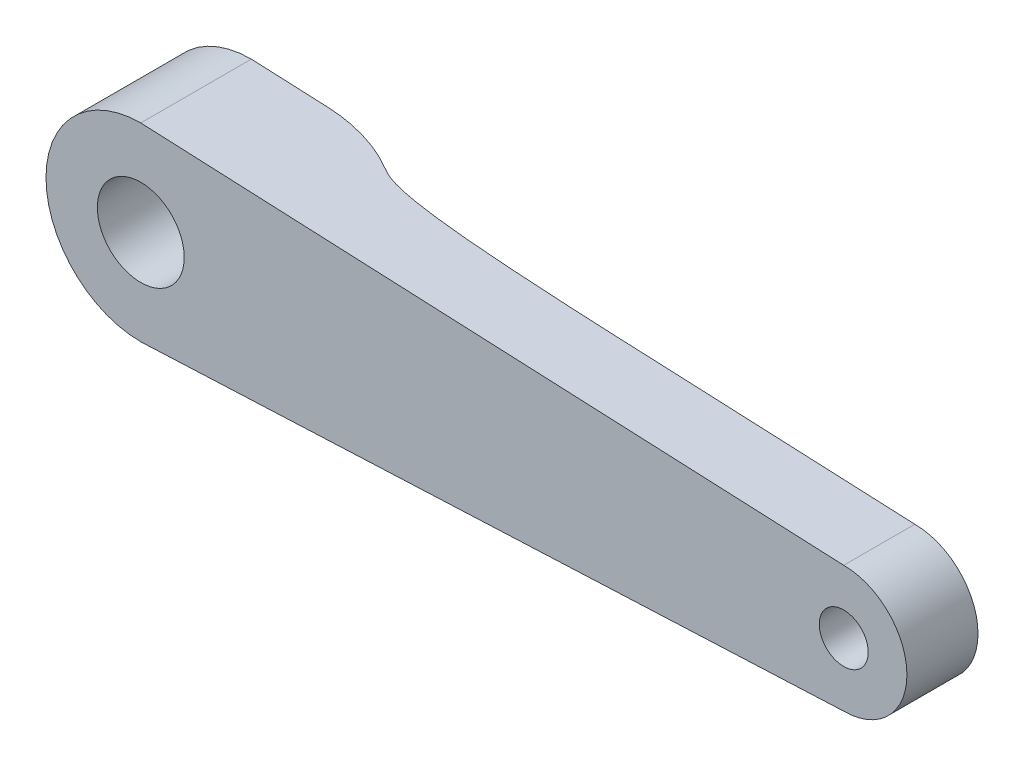
SolidWorks part; units mm, degrees
ref_plane "Ebene vorne" through (0, 0, 0) normal (0, 0, 1) x (1, 0, 0)
ref_plane "Ebene oben" through (0, 0, 0) normal (0, 1, 0) x (1, 0, 0)
ref_plane "Ebene rechts" through (0, 0, 0) normal (1, 0, 0) x (0, 0, -1)
sketch "Sketch1" plane through (0, 0, 0) normal (0, 0, 1) x (1, 0, 0)
  line L0 (0, 0) -> (44.5, 0) construction
  line L1 (0, 6) -> (44.5, 4)
  line L2 (0, -6) -> (44.5, -4)
  circle A1 centre (44.5, 0) radius 1.55
  circle A2 centre (0, 0) radius 6
  circle A3 centre (44.5, 0) radius 4
  dimension "D2" = 12
  dimension "D3" = 3.1
  dimension "D4" = 8
  dimension "D5" = 44.5
extrude "Boss-Extrude1" add sketch "Sketch1" along normal blind 7 contours A2 L0 A3 L1 | L1 A2 L2 | L0 A2 L2 A3 | A3 A1 region at (22.078, 2.5891, 0) region at (0, 0, 0) region at (22.078, -2.5891, 0) region at (41.7516, 2.7484, 0)
sketch "Sketch2" plane through (0, 0, 7) normal (0, 0, 1) x (1, 0, 0)
  circle A0 centre (0, 0) radius 2.75
  dimension "D1" = 5.5
extrude "Cut-Extrude1" cut sketch "Sketch2" against normal blind 5
sketch "Sketch3" plane through (0, 0, 0) normal (0, 0, -1) x (-1, 0, 0)
  circle A0 centre (0, 0) radius 1.75
  dimension "D1" = 3.5
extrude "Cut-Extrude2" cut sketch "Sketch3" against normal blind 5
sketch "Sketch5" plane through (0, 0, 0) normal (0, 1, 0) x (1, 0, 0)
  line L0 (48.5, 0) -> (48.5, -2.5)
  line L1 (48.5, -7) -> (48.5, 0) construction
  line L2 (48.5, -2.5) -> (28.5, -2.5)
  line L3 (-6, 0) -> (9, 0) construction
  line L4 (0, 0) -> (44.5, 0) construction
  line L5 (9, 0) -> (48.5, 0)
  spline S0 degree 3 poles (9, 0) (9.7345, -1.7321) (8.7722, -2.5787) (28.5, -2.5) knots 0 0 0 0 1 1 1 1
  dimension "D1" = 2.5
  dimension "D2" = 20
  dimension "D3" = 15
extrude "Cut-Extrude4" cut sketch "Sketch5" against normal through all and the other way through all
fillet "Fillet1" radius 10 1 edges at (9, 0, 0)
sketch3d "3DSketch1"
  line L0 (0, 0, 7) -> (44.5, 0, 7)
  line L1 (0, 0, 2) -> (0, 0, 7) construction
  line L2 (44.5, 0, 7) -> (44.5, 0, 2.5) construction
  line L3 (44.5, 0, 7) -> (44.5, 0, 2.5) construction
